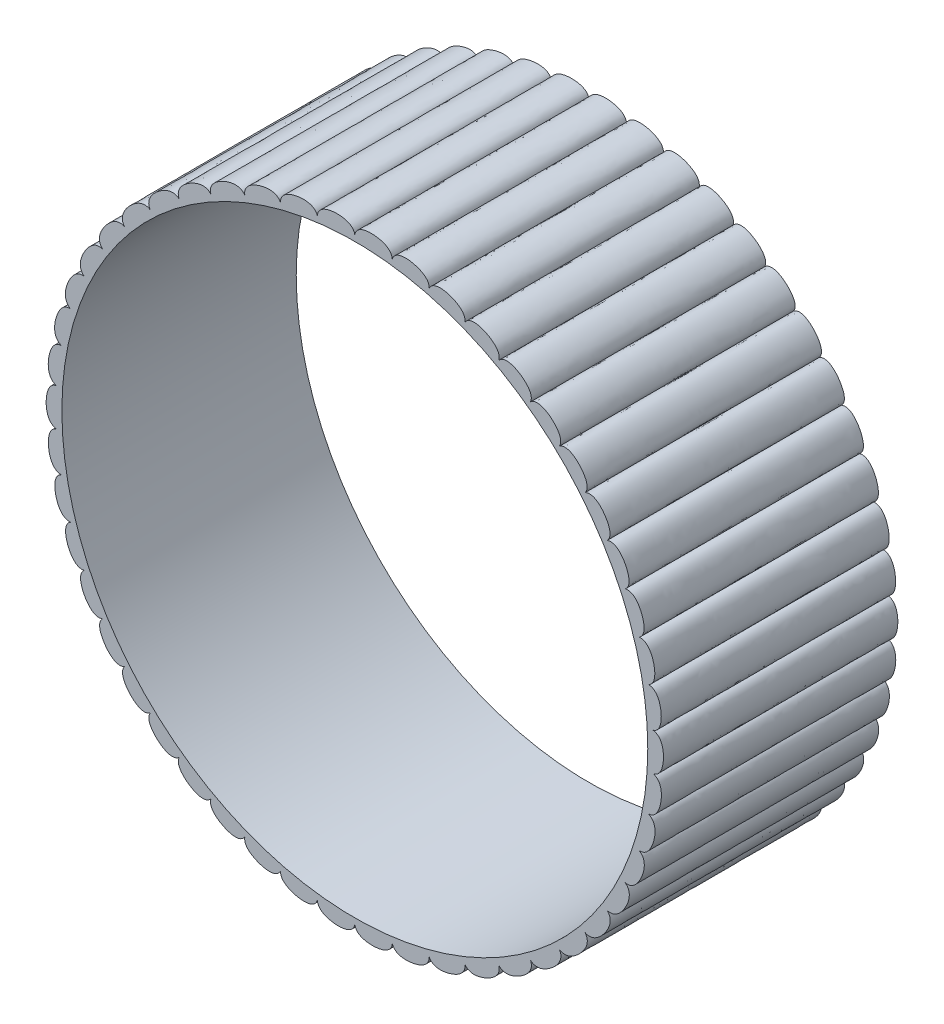
SolidWorks part; units mm, degrees
ref_plane "Front Plane" through (0, 0, 0) normal (0, 0, 1) x (1, 0, 0)
ref_plane "Top Plane" through (0, 0, 0) normal (0, 1, 0) x (1, 0, 0)
ref_plane "Right Plane" through (0, 0, 0) normal (1, 0, 0) x (0, 0, -1)
sketch "Sketch1" plane through (0, 0, 0) normal (0, 0, 1) x (1, 0, 0)
  line L0 (0, 0) -> (0, 25.5) construction
  line L1 (0, 0) -> (1.6012, 25.4497) construction
  line L2 (0, 0) -> (3.196, 25.2989) construction
  line L3 (0, 0) -> (4.7782, 25.0483) construction
  line L4 (0, 0) -> (6.3416, 24.6989) construction
  line L5 (0, 0) -> (7.8799, 24.2519) construction
  line L6 (0, 0) -> (9.3872, 23.7093) construction
  line L7 (0, 0) -> (10.8574, 23.0731) construction
  line L8 (0, 0) -> (12.2847, 22.3458) construction
  line L9 (0, 0) -> (13.6636, 21.5304) construction
  line L10 (0, 0) -> (14.9885, 20.6299) construction
  line L11 (0, 0) -> (16.2543, 19.6481) construction
  line L12 (0, 0) -> (17.456, 18.5887) construction
  line L13 (0, 0) -> (18.5887, 17.456) construction
  line L14 (0, 0) -> (19.6481, 16.2543) construction
  line L15 (0, 0) -> (20.6299, 14.9885) construction
  line L16 (0, 0) -> (21.5304, 13.6636) construction
  line L17 (0, 0) -> (22.3458, 12.2847) construction
  line L18 (0, 0) -> (23.0731, 10.8574) construction
  line L19 (0, 0) -> (23.7093, 9.3872) construction
  line L20 (0, 0) -> (24.2519, 7.8799) construction
  line L21 (0, 0) -> (24.6989, 6.3416) construction
  line L22 (0, 0) -> (25.0483, 4.7782) construction
  line L23 (0, 0) -> (25.2989, 3.196) construction
  line L24 (0, 0) -> (25.4497, 1.6012) construction
  line L25 (0, 0) -> (25.5, 0) construction
  line L26 (0, 0) -> (25.4497, -1.6012) construction
  line L27 (0, 0) -> (25.2989, -3.196) construction
  line L28 (0, 0) -> (25.0483, -4.7782) construction
  line L29 (0, 0) -> (24.6989, -6.3416) construction
  line L30 (0, 0) -> (24.2519, -7.8799) construction
  line L31 (0, 0) -> (23.7093, -9.3872) construction
  line L32 (0, 0) -> (23.0731, -10.8574) construction
  line L33 (0, 0) -> (22.3458, -12.2847) construction
  line L34 (0, 0) -> (21.5304, -13.6636) construction
  line L35 (0, 0) -> (20.6299, -14.9885) construction
  line L36 (0, 0) -> (19.6481, -16.2543) construction
  line L37 (0, 0) -> (18.5887, -17.456) construction
  line L38 (0, 0) -> (17.456, -18.5887) construction
  line L39 (0, 0) -> (16.2543, -19.6481) construction
  line L40 (0, 0) -> (14.9885, -20.6299) construction
  line L41 (0, 0) -> (13.6636, -21.5304) construction
  line L42 (0, 0) -> (12.2847, -22.3458) construction
  line L43 (0, 0) -> (10.8574, -23.0731) construction
  line L44 (0, 0) -> (9.3872, -23.7093) construction
  line L45 (0, 0) -> (7.8799, -24.2519) construction
  line L46 (0, 0) -> (6.3416, -24.6989) construction
  line L47 (0, 0) -> (4.7782, -25.0483) construction
  line L48 (0, 0) -> (3.196, -25.2989) construction
  line L49 (0, 0) -> (1.6012, -25.4497) construction
  line L50 (0, 25.5) -> (0, 28.397) construction
  line L51 (1.4985, 23.8176) -> (1.8054, 28.6959) construction
  line L52 (0, 0) -> (0, -25.5) construction
  line L53 (0, 0) -> (-1.6012, -25.4497) construction
  line L54 (0, 0) -> (-3.196, -25.2989) construction
  line L55 (0, 0) -> (-4.7782, -25.0483) construction
  line L56 (0, 0) -> (-6.3416, -24.6989) construction
  line L57 (0, 0) -> (-7.8799, -24.2519) construction
  line L58 (0, 0) -> (-9.3872, -23.7093) construction
  line L59 (0, 0) -> (-10.8574, -23.0731) construction
  line L60 (0, 0) -> (-12.2847, -22.3458) construction
  line L61 (0, 0) -> (-13.6636, -21.5304) construction
  line L62 (0, 0) -> (-14.9885, -20.6299) construction
  line L63 (0, 0) -> (-16.2543, -19.6481) construction
  line L64 (0, 0) -> (-17.456, -18.5887) construction
  line L65 (0, 0) -> (-18.5887, -17.456) construction
  line L66 (0, 0) -> (-19.6481, -16.2543) construction
  line L67 (0, 0) -> (-20.6299, -14.9885) construction
  line L68 (0, 0) -> (-21.5304, -13.6636) construction
  line L69 (0, 0) -> (-22.3458, -12.2847) construction
  line L70 (0, 0) -> (-23.0731, -10.8574) construction
  line L71 (0, 0) -> (-23.7093, -9.3872) construction
  line L72 (0, 0) -> (-24.2519, -7.8799) construction
  line L73 (0, 0) -> (-24.6989, -6.3416) construction
  line L74 (0, 0) -> (-25.0483, -4.7782) construction
  line L75 (0, 0) -> (-25.2989, -3.196) construction
  line L76 (0, 0) -> (-25.4497, -1.6012) construction
  line L77 (0, 0) -> (-25.5, 0) construction
  line L78 (0, 0) -> (-25.4497, 1.6012) construction
  line L79 (0, 0) -> (-25.2989, 3.196) construction
  line L80 (0, 0) -> (-25.0483, 4.7782) construction
  line L81 (0, 0) -> (-24.6989, 6.3416) construction
  line L82 (0, 0) -> (-24.2519, 7.8799) construction
  line L83 (0, 0) -> (-23.7093, 9.3872) construction
  line L84 (0, 0) -> (-23.0731, 10.8574) construction
  line L85 (0, 0) -> (-22.3458, 12.2847) construction
  line L86 (0, 0) -> (-21.5304, 13.6636) construction
  line L87 (0, 0) -> (-20.6299, 14.9885) construction
  line L88 (0, 0) -> (-19.6481, 16.2543) construction
  line L89 (0, 0) -> (-18.5887, 17.456) construction
  line L90 (0, 0) -> (-17.456, 18.5887) construction
  line L91 (0, 0) -> (-16.2543, 19.6481) construction
  line L92 (0, 0) -> (-14.9885, 20.6299) construction
  line L93 (0, 0) -> (-13.6636, 21.5304) construction
  line L94 (0, 0) -> (-12.2847, 22.3458) construction
  line L95 (0, 0) -> (-10.8574, 23.0731) construction
  line L96 (0, 0) -> (-9.3872, 23.7093) construction
  line L97 (0, 0) -> (-7.8799, 24.2519) construction
  line L98 (0, 0) -> (-6.3416, 24.6989) construction
  line L99 (0, 0) -> (-4.7782, 25.0483) construction
  line L100 (0, 0) -> (-3.196, 25.2989) construction
  line L101 (0, 0) -> (-1.6012, 25.4497) construction
  circle A0 centre (0, 0) radius 25
  arc A1 (0, 25.5) -> (12.2847, 22.3458) centre (0, 0) ccw construction
  circle A2 centre (0, 0) radius 25.5 construction
  spline S0 degree 3 poles (0, 25.5) (0.1239, 26.1202) (0.9461, 26.3461) (2.4071, 26.2264) (3.1486, 25.8843) (3.196, 25.2989) knots 0 0 0 0 0.438491 0.538491 1 1 1 1
  spline S1 degree 3 poles (3.196, 25.2989) (3.3967, 25.8987) (4.2407, 26.0198) (5.6752, 25.7179) (6.3679, 25.2856) (6.3416, 24.6989) knots 0 0 0 0 0.438491 0.538491 1 1 1 1
  spline S2 degree 3 poles (6.3416, 24.6989) (6.6159, 25.2688) (7.4684, 25.2831) (8.8537, 24.8038) (9.4868, 24.2881) (9.3872, 23.7093) knots 0 0 0 0 0.438491 0.538491 1 1 1 1
  spline S3 degree 3 poles (9.3872, 23.7093) (9.7307, 24.2404) (10.5783, 24.1477) (11.8927, 23.4985) (12.4561, 22.9075) (12.2847, 22.3458) knots 0 0 0 0 0.438491 0.538491 1 1 1 1
  spline S4 degree 3 poles (12.2847, 22.3458) (12.6921, 22.8296) (13.5214, 22.6315) (14.744, 21.8227) (15.229, 21.1657) (14.9885, 20.6299) knots 0 0 0 0 0.438491 0.538491 1 1 1 1
  spline S5 degree 3 poles (14.9885, 20.6299) (15.4533, 21.0589) (16.2513, 20.7583) (17.3629, 19.8027) (17.7617, 19.0901) (17.456, 18.5887) knots 0 0 0 0 0.438491 0.538491 1 1 1 1
  spline S6 degree 3 poles (17.456, 18.5887) (17.9709, 18.956) (18.7249, 18.5578) (19.7079, 17.4704) (20.0142, 16.7135) (19.6481, 16.2543) knots 0 0 0 0 0.438491 0.538491 1 1 1 1
  spline S7 degree 3 poles (19.6481, 16.2543) (20.205, 16.5542) (20.9031, 16.0646) (21.7421, 14.8626) (21.9512, 14.0732) (21.5304, 13.6636) knots 0 0 0 0 0.438491 0.538491 1 1 1 1
  spline S8 degree 3 poles (21.5304, 13.6636) (22.1204, 13.8913) (22.7517, 13.3181) (23.4335, 12.0204) (23.5419, 11.2111) (23.0731, 10.8574) knots 0 0 0 0 0.438491 0.538491 1 1 1 1
  spline S9 degree 3 poles (23.0731, 10.8574) (23.687, 11.0093) (24.2415, 10.3615) (24.7552, 8.9886) (24.7614, 8.1721) (24.2519, 7.8799) knots 0 0 0 0 0.438491 0.538491 1 1 1 1
  spline S10 degree 3 poles (24.2519, 7.8799) (24.8801, 7.9537) (25.349, 7.2416) (25.6866, 5.8151) (25.5904, 5.0042) (25.0483, 4.7782) knots 0 0 0 0 0.438491 0.538491 1 1 1 1
  spline S11 degree 3 poles (25.0483, 4.7782) (25.6808, 4.7727) (26.0567, 4.0074) (26.2129, 2.5498) (26.0158, 1.7574) (25.4497, 1.6012) knots 0 0 0 0 0.438491 0.538491 1 1 1 1
  spline S12 degree 3 poles (25.4497, 1.6012) (26.0765, 1.5164) (26.3535, 0.71) (26.3258, -0.7556) (26.0309, -1.5171) (25.4497, -1.6012) knots 0 0 0 0 0.438491 0.538491 1 1 1 1
  spline S13 degree 3 poles (25.4497, -1.6012) (26.0609, -1.7638) (26.2347, -2.5985) (26.0235, -4.0491) (25.6355, -4.7677) (25.0483, -4.7782) knots 0 0 0 0 0.438491 0.538491 1 1 1 1
  spline S14 degree 3 poles (25.0483, -4.7782) (25.6343, -5.0162) (25.7022, -5.8661) (25.3108, -7.2788) (24.8358, -7.943) (24.2519, -7.8799) knots 0 0 0 0 0.438491 0.538491 1 1 1 1
  spline S15 degree 3 poles (24.2519, -7.8799) (24.8035, -8.1894) (24.7643, -9.0412) (24.1989, -10.3937) (23.6444, -10.9932) (23.0731, -10.8574) knots 0 0 0 0 0.438491 0.538491 1 1 1 1
  spline S16 degree 3 poles (23.0731, -10.8574) (23.5815, -11.2336) (23.4358, -12.0737) (22.7054, -13.3447) (22.0802, -13.8699) (21.5304, -13.6636) knots 0 0 0 0 0.438491 0.538491 1 1 1 1
  spline S17 degree 3 poles (21.5304, -13.6636) (21.9876, -14.1005) (21.7378, -14.9158) (20.8538, -16.0852) (20.1677, -16.5279) (19.6481, -16.2543) knots 0 0 0 0 0.438491 0.538491 1 1 1 1
  spline S18 degree 3 poles (19.6481, -16.2543) (20.047, -16.7451) (19.6969, -17.5226) (18.6734, -18.572) (17.9372, -18.9253) (17.456, -18.5887) knots 0 0 0 0 0.438491 0.538491 1 1 1 1
  spline S19 degree 3 poles (17.456, -18.5887) (17.7902, -19.1257) (17.3455, -19.8532) (16.1985, -20.766) (15.4238, -21.0242) (14.9885, -20.6299) knots 0 0 0 0 0.438491 0.538491 1 1 1 1
  spline S20 degree 3 poles (14.9885, -20.6299) (15.2528, -21.2045) (14.7204, -21.8706) (13.4681, -22.6324) (12.6671, -22.7915) (12.2847, -22.3458) knots 0 0 0 0 0.438491 0.538491 1 1 1 1
  spline S21 degree 3 poles (12.2847, -22.3458) (12.4749, -22.949) (11.8632, -23.5431) (10.5253, -24.142) (9.7107, -24.1994) (9.3872, -23.7093) knots 0 0 0 0 0.438491 0.538491 1 1 1 1
  spline S22 degree 3 poles (9.3872, -23.7093) (9.5003, -24.3316) (8.819, -24.8443) (7.4165, -25.2708) (6.6012, -25.2257) (6.3416, -24.6989) knots 0 0 0 0 0.438491 0.538491 1 1 1 1
  spline S23 degree 3 poles (6.3416, -24.6989) (6.3758, -25.3304) (5.6356, -25.7537) (4.1907, -26.001) (3.3875, -25.8541) (3.196, -25.2989) knots 0 0 0 0 0.438491 0.538491 1 1 1 1
  spline S24 degree 3 poles (3.196, -25.2989) (3.1508, -25.9298) (2.3634, -26.2569) (0.8989, -26.3213) (0.1204, -26.0748) (0, -25.5) knots 0 0 0 0 0.438491 0.538491 1 1 1 1
  spline S25 degree 3 poles (0, -25.5) (-0.1239, -26.1202) (-0.9461, -26.3461) (-2.4071, -26.2264) (-3.1486, -25.8843) (-3.196, -25.2989) knots 0 0 0 0 0.438491 0.538491 1 1 1 1
  spline S26 degree 3 poles (-3.196, -25.2989) (-3.3967, -25.8987) (-4.2407, -26.0198) (-5.6752, -25.7179) (-6.3679, -25.2856) (-6.3416, -24.6989) knots 0 0 0 0 0.438491 0.538491 1 1 1 1
  spline S27 degree 3 poles (-6.3416, -24.6989) (-6.6159, -25.2688) (-7.4684, -25.2831) (-8.8537, -24.8038) (-9.4868, -24.2881) (-9.3872, -23.7093) knots 0 0 0 0 0.438491 0.538491 1 1 1 1
  spline S28 degree 3 poles (-9.3872, -23.7093) (-9.7307, -24.2404) (-10.5783, -24.1477) (-11.8927, -23.4985) (-12.4561, -22.9075) (-12.2847, -22.3458) knots 0 0 0 0 0.438491 0.538491 1 1 1 1
  spline S29 degree 3 poles (-12.2847, -22.3458) (-12.6921, -22.8296) (-13.5214, -22.6315) (-14.744, -21.8227) (-15.229, -21.1657) (-14.9885, -20.6299) knots 0 0 0 0 0.438491 0.538491 1 1 1 1
  spline S30 degree 3 poles (-14.9885, -20.6299) (-15.4533, -21.0589) (-16.2513, -20.7583) (-17.3629, -19.8027) (-17.7617, -19.0901) (-17.456, -18.5887) knots 0 0 0 0 0.438491 0.538491 1 1 1 1
  spline S31 degree 3 poles (-17.456, -18.5887) (-17.9709, -18.956) (-18.7249, -18.5578) (-19.7079, -17.4704) (-20.0142, -16.7135) (-19.6481, -16.2543) knots 0 0 0 0 0.438491 0.538491 1 1 1 1
  spline S32 degree 3 poles (-19.6481, -16.2543) (-20.205, -16.5542) (-20.9031, -16.0646) (-21.7421, -14.8626) (-21.9512, -14.0732) (-21.5304, -13.6636) knots 0 0 0 0 0.438491 0.538491 1 1 1 1
  spline S33 degree 3 poles (-21.5304, -13.6636) (-22.1204, -13.8913) (-22.7517, -13.3181) (-23.4335, -12.0204) (-23.5419, -11.2111) (-23.0731, -10.8574) knots 0 0 0 0 0.438491 0.538491 1 1 1 1
  spline S34 degree 3 poles (-23.0731, -10.8574) (-23.687, -11.0093) (-24.2415, -10.3615) (-24.7552, -8.9886) (-24.7614, -8.1721) (-24.2519, -7.8799) knots 0 0 0 0 0.438491 0.538491 1 1 1 1
  spline S35 degree 3 poles (-24.2519, -7.8799) (-24.8801, -7.9537) (-25.349, -7.2416) (-25.6866, -5.8151) (-25.5904, -5.0042) (-25.0483, -4.7782) knots 0 0 0 0 0.438491 0.538491 1 1 1 1
  spline S36 degree 3 poles (-25.0483, -4.7782) (-25.6808, -4.7727) (-26.0567, -4.0074) (-26.2129, -2.5498) (-26.0158, -1.7574) (-25.4497, -1.6012) knots 0 0 0 0 0.438491 0.538491 1 1 1 1
  spline S37 degree 3 poles (-25.4497, -1.6012) (-26.0765, -1.5164) (-26.3535, -0.71) (-26.3258, 0.7556) (-26.0309, 1.5171) (-25.4497, 1.6012) knots 0 0 0 0 0.438491 0.538491 1 1 1 1
  spline S38 degree 3 poles (-25.4497, 1.6012) (-26.0609, 1.7638) (-26.2347, 2.5985) (-26.0235, 4.0491) (-25.6355, 4.7677) (-25.0483, 4.7782) knots 0 0 0 0 0.438491 0.538491 1 1 1 1
  spline S39 degree 3 poles (-25.0483, 4.7782) (-25.6343, 5.0162) (-25.7022, 5.8661) (-25.3108, 7.2788) (-24.8358, 7.943) (-24.2519, 7.8799) knots 0 0 0 0 0.438491 0.538491 1 1 1 1
  spline S40 degree 3 poles (-24.2519, 7.8799) (-24.8035, 8.1894) (-24.7643, 9.0412) (-24.1989, 10.3937) (-23.6444, 10.9932) (-23.0731, 10.8574) knots 0 0 0 0 0.438491 0.538491 1 1 1 1
  spline S41 degree 3 poles (-23.0731, 10.8574) (-23.5815, 11.2336) (-23.4358, 12.0737) (-22.7054, 13.3447) (-22.0802, 13.8699) (-21.5304, 13.6636) knots 0 0 0 0 0.438491 0.538491 1 1 1 1
  spline S42 degree 3 poles (-21.5304, 13.6636) (-21.9876, 14.1005) (-21.7378, 14.9158) (-20.8538, 16.0852) (-20.1677, 16.5279) (-19.6481, 16.2543) knots 0 0 0 0 0.438491 0.538491 1 1 1 1
  spline S43 degree 3 poles (-19.6481, 16.2543) (-20.047, 16.7451) (-19.6969, 17.5226) (-18.6734, 18.572) (-17.9372, 18.9253) (-17.456, 18.5887) knots 0 0 0 0 0.438491 0.538491 1 1 1 1
  spline S44 degree 3 poles (-17.456, 18.5887) (-17.7902, 19.1257) (-17.3455, 19.8532) (-16.1985, 20.766) (-15.4238, 21.0242) (-14.9885, 20.6299) knots 0 0 0 0 0.438491 0.538491 1 1 1 1
  spline S45 degree 3 poles (-14.9885, 20.6299) (-15.2528, 21.2045) (-14.7204, 21.8706) (-13.4681, 22.6324) (-12.6671, 22.7915) (-12.2847, 22.3458) knots 0 0 0 0 0.438491 0.538491 1 1 1 1
  spline S46 degree 3 poles (-12.2847, 22.3458) (-12.4749, 22.949) (-11.8632, 23.5431) (-10.5253, 24.142) (-9.7107, 24.1994) (-9.3872, 23.7093) knots 0 0 0 0 0.438491 0.538491 1 1 1 1
  spline S47 degree 3 poles (-9.3872, 23.7093) (-9.5003, 24.3316) (-8.819, 24.8443) (-7.4165, 25.2708) (-6.6012, 25.2257) (-6.3416, 24.6989) knots 0 0 0 0 0.438491 0.538491 1 1 1 1
  spline S48 degree 3 poles (-6.3416, 24.6989) (-6.3758, 25.3304) (-5.6356, 25.7537) (-4.1907, 26.001) (-3.3875, 25.8541) (-3.196, 25.2989) knots 0 0 0 0 0.438491 0.538491 1 1 1 1
  spline S49 degree 3 poles (-3.196, 25.2989) (-3.1508, 25.9298) (-2.3634, 26.2569) (-0.8989, 26.3213) (-0.1204, 26.0748) (0, 25.5) knots 0 0 0 0 0.438491 0.538491 1 1 1 1
  dimension "D3" = 100
extrude "Boss-Extrude1" add sketch "Sketch1" along normal blind 20 contours S0 region at (1.5895, 25.5441, 0)
